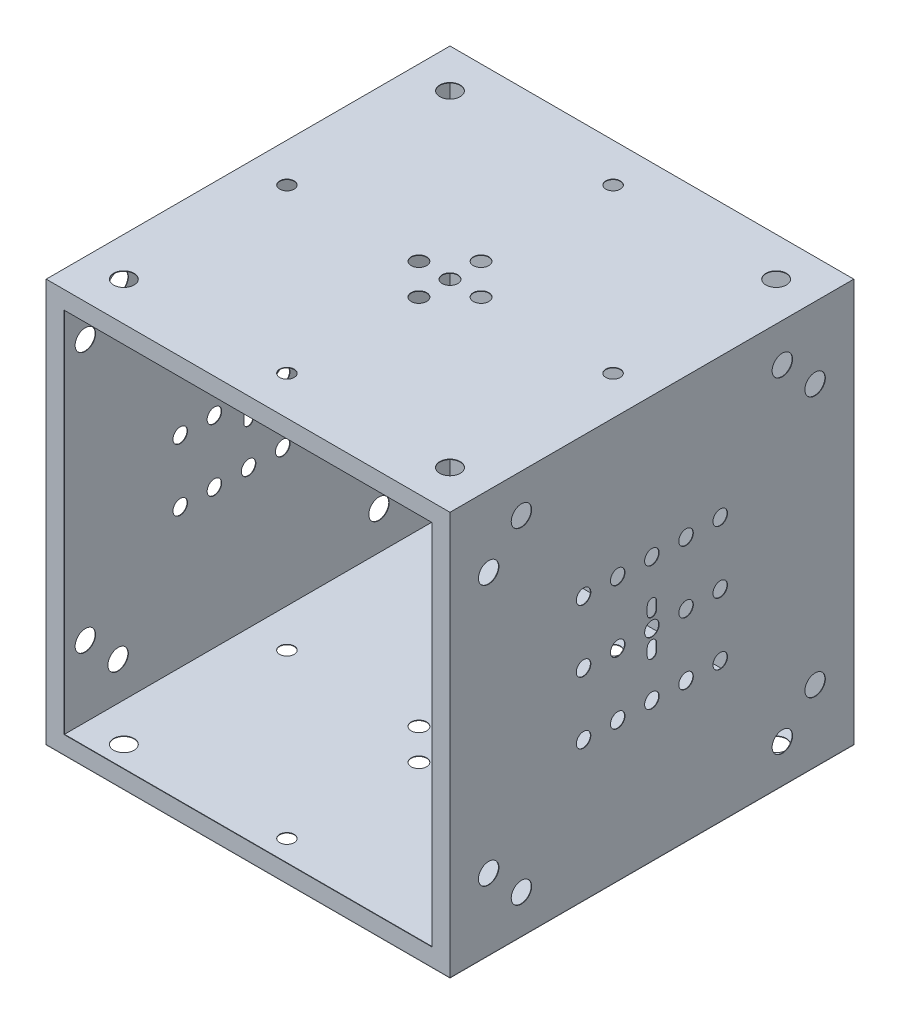
SolidWorks part; units mm, degrees
ref_plane "Front" through (0, 0, 0) normal (0, 0, 1) x (1, 0, 0)
ref_plane "Top" through (0, 0, 0) normal (0, 1, 0) x (1, 0, 0)
ref_plane "Right" through (0, 0, 0) normal (1, 0, 0) x (0, 0, -1)
sketch "Sketch1" plane through (0, 0, 0) normal (0, 1, 0) x (1, 0, 0)
  line L1 (-1300, 1300) -> (1300, 1300)
  line L2 (-1300, 1300) -> (-1300, -1300)
  line L3 (-1300, -1300) -> (1300, -1300)
  line L4 (1300, 1300) -> (1300, -1300)
  line L5 (-1300, 1300) -> (1300, -1300) construction
  line L6 (-1300, -1300) -> (1300, 1300) construction
  point P0 (0, 0)
  dimension "D1" = 2600
  dimension "D2" = 2600
extrude "Boss-Extrude1" add sketch "Sketch1" along normal blind 2597
shell "Shell1" thickness 3 removed face at (0, 1298.5, 1300)
sketch "Sketch3" plane through (0, 0, 1300) normal (0, 0, 1) x (1, 0, 0)
  line L0 (-1300, 2597) -> (1300, 0) construction
  line L1 (-1300, 0) -> (1300, 2597) construction
  line L2 (1300, 2597) -> (1300, 0) construction
  line L3 (-1300, 2597) -> (1300, 2597) construction
  line L5 (-1300, 0) -> (1300, 0)
  line L6 (-1300, 0) -> (-1300, 2597)
  line L7 (-1300, 2597) -> (1300, 2597)
  line L8 (1300, 0) -> (1300, 2597)
  line L9 (-1300, 0) -> (1300, 2597) construction
  line L10 (-1300, 2597) -> (1300, 0) construction
  line L11 (-1185, 115) -> (1185, 115)
  line L12 (-1185, 115) -> (-1185, 2482)
  line L13 (-1185, 2482) -> (1185, 2482)
  line L14 (1185, 115) -> (1185, 2482)
  line L15 (-1185, 115) -> (1185, 2482) construction
  line L16 (-1185, 2482) -> (1185, 115) construction
  point P11 (0, 1298.5)
  point P12 (0, 1298.5)
  dimension "D1" = 115
  dimension "D2" = 115
extrude "Boss-Extrude2" add sketch "Sketch3" against normal blind 3
sketch "Sketch4" plane through (0, 2597, 0) normal (0, 1, 0) x (1, 0, 0)
  line L0 (-1300, 0) -> (1300, 0) construction
  line L1 (-1300, 1300) -> (-1300, -1300) construction
  line L2 (1300, -1300) -> (1300, 1300) construction
  line L3 (0, 1300) -> (0, -1300) construction
  line L4 (1300, 1300) -> (-1300, 1300) construction
  line L5 (-1300, -1300) -> (1300, -1300) construction
  line L6 (0, 0) -> (1300, 1300) construction
  line L7 (0, 0) -> (0, 200) construction
  circle A0 centre (0, 0) radius 49.85
  circle A4 centre (0, 200) radius 49.85
  circle A5 centre (0, 1050) radius 46.75
  circle A7 centre (1050, 1050) radius 65.8
  circle A8 centre (200, 0) radius 49.85
  circle A9 centre (1050, 0) radius 46.75
  circle A10 centre (1050, -1050) radius 65.8
  circle A11 centre (0, -200) radius 49.85
  circle A12 centre (0, -1050) radius 46.75
  circle A13 centre (-1050, -1050) radius 65.8
  circle A14 centre (-1050, 0) radius 46.75
  circle A15 centre (-200, 0) radius 49.85
  circle A16 centre (-1050, 1050) radius 65.8
  dimension "D1" = 99.7
  dimension "D2" = 131.6
  dimension "D6" = 93.5
  dimension "D3" = 1050
  dimension "D5" = 200
  dimension "D7" = 1050
  dimension "D4" = 2
extrude "Cut-Extrude1" cut sketch "Sketch4" against normal through all
sketch "Sketch5" plane through (0, 0, -1300) normal (0, 0, -1) x (-1, 0, 0)
  line L0 (-1300, 1298.5) -> (1300, 1298.5) construction
  line L1 (-1300, 2597) -> (-1300, 0) construction
  line L2 (1300, 2597) -> (1300, 0) construction
  line L3 (0, 0) -> (0, 2597) construction
  line L4 (-1300, 2597) -> (1300, 2597) construction
  line L5 (-1300, 2597) -> (0, 1298.5) construction
  circle A0 centre (0, 1298.5) radius 91.2
  circle A1 centre (0, 1438.5) radius 35.635
  circle A2 centre (-222, 1680.5) radius 91.2
  circle A3 centre (222, 916.5) radius 91.2
  circle A4 centre (-900, 2197.4615) radius 65.8
  circle A5 centre (0, 1158.5) radius 35.635
  circle A6 centre (-900, 399.5385) radius 65.8
  circle A7 centre (900, 399.5385) radius 65.8
  circle A8 centre (900, 2197.4615) radius 65.8
  dimension "D1" = 182.4
  dimension "D2" = 71.27
  dimension "D4" = 182.4
  dimension "D9" = 182.4
  dimension "D10" = 131.6
  dimension "D3" = 140
  dimension "D5" = 222
  dimension "D6" = 382
  dimension "D7" = 222
  dimension "D8" = 382
  dimension "D11" = 900
extrude "Cut-Extrude2" cut sketch "Sketch5" against normal through all
sketch "Sketch6" plane through (-1300, 0, 0) normal (-1, 0, 0) x (0, 0, 1)
  line L0 (-1300, 1298.5) -> (1300, 1298.5) construction
  line L1 (-1300, 2597) -> (-1300, 0) construction
  line L2 (1300, 2597) -> (1300, 0) construction
  line L3 (0, 2597) -> (0, 0) construction
  line L4 (-1300, 2597) -> (1300, 2597) construction
  line L5 (0, 1298.5) -> (-1297, 2594) construction
  line L6 (0, 1438.5) -> (0, 1391) construction
  line L7 (30, 1438.5) -> (30, 1391)
  line L8 (-30, 1438.5) -> (-30, 1391)
  line L9 (0, 1298.5) -> (0, 1698.5) construction
  line L10 (0, 1698.5) -> (-220, 1698.5) construction
  line L11 (0, 1158.5) -> (0, 1206) construction
  line L12 (30, 1158.5) -> (30, 1206)
  line L13 (-30, 1158.5) -> (-30, 1206)
  circle A0 centre (0, 1298.5) radius 46.75
  arc A1 (30, 1438.5) -> (-30, 1438.5) centre (0, 1438.5) ccw
  arc A2 (-30, 1391) -> (30, 1391) centre (0, 1391) ccw
  circle A3 centre (0, 1698.5) radius 46.75
  circle A4 centre (-220, 1698.5) radius 46.75
  circle A5 centre (-220, 1298.5) radius 46.75
  circle A6 centre (-440, 1698.5) radius 46.75
  circle A7 centre (-440, 1298.5) radius 46.75
  circle A8 centre (-840, 2348.5) radius 65.8
  circle A9 centre (-1050.9713, 2137.2844) radius 65.8
  circle A10 centre (220, 1298.5) radius 46.75
  circle A11 centre (440, 1298.5) radius 46.75
  circle A12 centre (440, 1698.5) radius 46.75
  circle A13 centre (220, 1698.5) radius 46.75
  circle A14 centre (1050.9713, 2137.2844) radius 65.8
  circle A15 centre (840, 2348.5) radius 65.8
  arc A16 (30, 1158.5) -> (-30, 1158.5) centre (0, 1158.5) cw
  arc A17 (-30, 1206) -> (30, 1206) centre (0, 1206) cw
  circle A18 centre (-440, 898.5) radius 46.75
  circle A19 centre (-220, 898.5) radius 46.75
  circle A20 centre (0, 898.5) radius 46.75
  circle A21 centre (220, 898.5) radius 46.75
  circle A22 centre (440, 898.5) radius 46.75
  circle A23 centre (1050.9713, 459.7156) radius 65.8
  circle A24 centre (840, 248.5) radius 65.8
  circle A25 centre (-840, 248.5) radius 65.8
  circle A26 centre (-1050.9713, 459.7156) radius 65.8
  point P17 (0, 1414.75)
  point P53 (0, 1182.25)
  dimension "D1" = 93.5
  dimension "D2" = 30
  dimension "D9" = 131.6
  dimension "D3" = 47.5
  dimension "D4" = 92.5
  dimension "D6" = 400
  dimension "D8" = 220
  dimension "D10" = 1050
  dimension "D11" = 840
  dimension "D5" = 2
  dimension "D7" = 3
extrude "Cut-Extrude3" cut sketch "Sketch6" against normal through all
split "Split1" bodies to split 107 resulting bodies 108 109 split by face at (-1050, 3, 1115.8)
